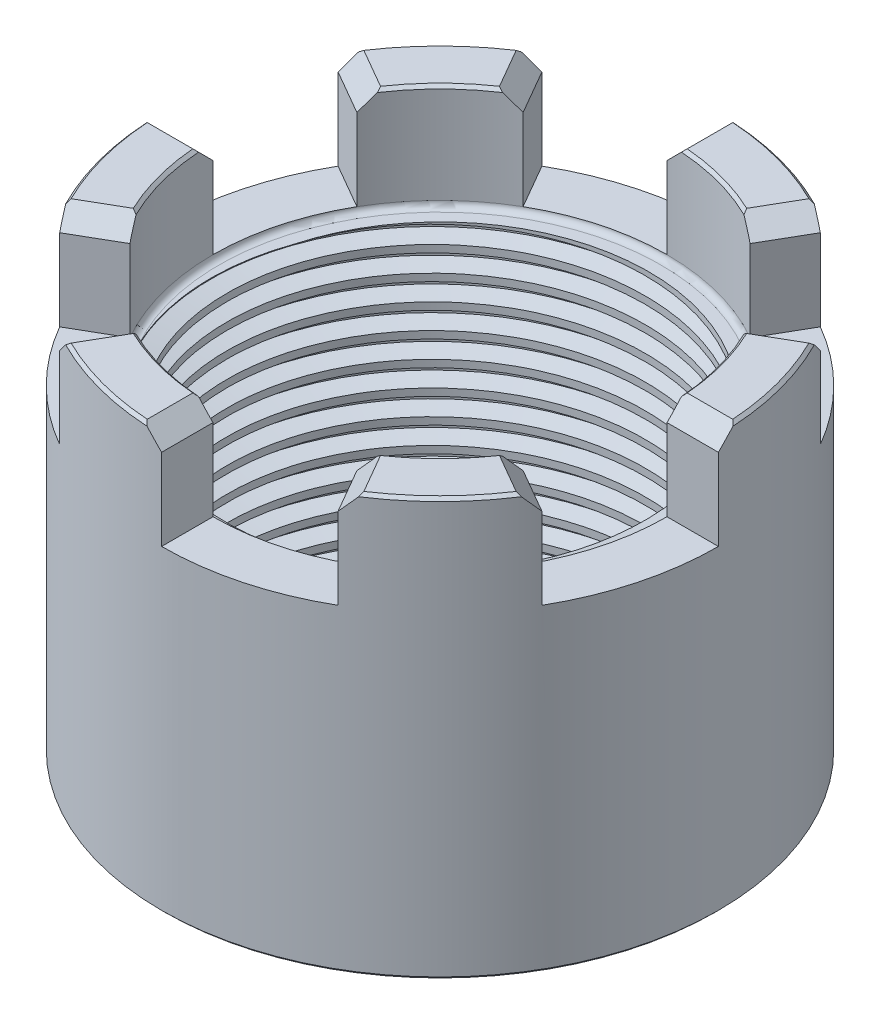
SolidWorks part; units mm, degrees
ref_plane "Front Plane" through (0, 0, 0) normal (0, 0, 1) x (1, 0, 0)
ref_plane "Top Plane" through (0, 0, 0) normal (0, 1, 0) x (1, 0, 0)
ref_plane "Right Plane" through (0, 0, 0) normal (1, 0, 0) x (0, 0, -1)
sketch "Sketch1" plane through (0, 0, 0) normal (0, 1, 0) x (1, 0, 0)
  circle A0 centre (0, 0) radius 35.56
  dimension "D1" = 71.12
extrude "Boss-Extrude1" add sketch "Sketch1" along normal blind 40.64
sketch "Sketch2" plane through (0, 40.64, 0) normal (0, 1, 0) x (1, 0, 0)
  circle A0 centre (0, 0) radius 26.7018
  dimension "D1" = 53.4035
extrude "Cut-Extrude1" cut sketch "Sketch2" against normal blind 67.31
sketch "Sketch3" plane through (0, 40.64, 0) normal (0, 1, 0) x (1, 0, 0)
  line L0 (-28.9941, 0) -> (-35.56, 0)
  line L1 (-25.1096, -14.4971) -> (-30.7959, -17.78)
  line L2 (-25.1096, 14.4971) -> (-30.7959, 17.78)
  line L3 (-14.497, 25.1096) -> (-17.78, 30.7959)
  line L4 (0, 28.9941) -> (0, 35.56)
  line L5 (14.4971, 25.1096) -> (17.78, 30.7959)
  line L6 (25.1096, 14.497) -> (30.7959, 17.78)
  line L7 (28.9941, 0) -> (35.56, 0)
  line L8 (25.1096, -14.4971) -> (30.7959, -17.78)
  line L9 (14.497, -25.1096) -> (17.78, -30.7959)
  line L10 (0, -28.9941) -> (0, -35.56)
  line L11 (-14.4971, -25.1096) -> (-17.78, -30.7959)
  arc A0 (-35.56, 0) -> (-30.7959, -17.78) centre (0, 0) ccw
  arc A1 (-28.9941, 0) -> (-25.1096, -14.4971) centre (0, 0) ccw
  arc A2 (-17.78, 30.7959) -> (-30.7959, 17.78) centre (0, 0) ccw
  arc A3 (-14.497, 25.1096) -> (-25.1096, 14.4971) centre (0, 0) ccw
  arc A4 (17.78, 30.7959) -> (0, 35.56) centre (0, 0) ccw
  arc A5 (14.4971, 25.1096) -> (0, 28.9941) centre (0, 0) ccw
  arc A6 (35.56, 0) -> (30.7959, 17.78) centre (0, 0) ccw
  arc A7 (28.9941, 0) -> (25.1096, 14.497) centre (0, 0) ccw
  arc A8 (17.78, -30.7959) -> (30.7959, -17.78) centre (0, 0) ccw
  arc A9 (14.497, -25.1096) -> (25.1096, -14.4971) centre (0, 0) ccw
  arc A10 (-17.78, -30.7959) -> (0, -35.56) centre (0, 0) ccw
  arc A11 (-14.4971, -25.1096) -> (0, -28.9941) centre (0, 0) ccw
  point P29 (0, 0)
  dimension "D2" = 57.9882
  dimension "D1" = 30
  dimension "D3" = 6
extrude "Boss-Extrude2" add sketch "Sketch3" along normal blind 12.7
chamfer "Chamfer1" distance 2.286 angle 45 1 edges at (0, 53.34, 32.2771)
chamfer "Chamfer2" distance 2.286 angle 45 1 edges at (-16.1385, 53.34, 27.9527)
chamfer "Chamfer3" distance 2.286 angle 45 1 edges at (-27.9527, 53.34, 16.1385)
chamfer "Chamfer4" distance 2.286 angle 45 1 edges at (16.1385, 53.34, 27.9527)
chamfer "Chamfer5" distance 2.286 angle 45 1 edges at (27.9527, 53.34, 16.1385)
chamfer "Chamfer6" distance 2.286 angle 45 1 edges at (32.277, 53.34, 0)
chamfer "Chamfer7" distance 2.286 angle 45 1 edges at (27.9527, 53.34, -16.1385)
chamfer "Chamfer8" distance 2.286 angle 45 1 edges at (16.1385, 53.34, -27.9527)
chamfer "Chamfer9" distance 2.286 angle 45 1 edges at (0, 53.34, -32.2771)
chamfer "Chamfer10" distance 2.286 angle 45 1 edges at (-16.1385, 53.34, -27.9527)
chamfer "Chamfer11" distance 2.286 angle 45 1 edges at (-27.9527, 53.34, -16.1385)
chamfer "Chamfer12" distance 2.286 angle 45 1 edges at (-32.2771, 53.34, 0)
chamfer "Chamfer13" distance 0.381 angle 45 1 edges at (9.2036, 53.34, -34.3483)
chamfer "Chamfer14" distance 0.381 angle 45 1 edges at (-25.1447, 53.34, -25.1447)
chamfer "Chamfer15" distance 0.381 angle 45 1 edges at (-34.3483, 53.34, 9.2036)
chamfer "Chamfer16" distance 0.381 angle 45 1 edges at (-9.2036, 53.34, 34.3483)
chamfer "Chamfer17" distance 0.381 angle 45 1 edges at (25.1447, 53.34, 25.1447)
chamfer "Chamfer18" distance 0.381 angle 45 1 edges at (34.3483, 53.34, -9.2036)
chamfer "Chamfer20" distance 0.381 angle 45 1 edges at (-28.0062, 53.34, 7.5042)
chamfer "Chamfer21" distance 0.381 angle 45 1 edges at (-7.5042, 53.34, 28.0062)
chamfer "Chamfer22" distance 0.381 angle 45 1 edges at (20.5019, 53.34, 20.5019)
chamfer "Chamfer23" distance 0.381 angle 45 1 edges at (-20.5019, 53.34, -20.5019)
chamfer "Chamfer24" distance 0.381 angle 45 1 edges at (7.5042, 53.34, -28.0062)
chamfer "Chamfer25" distance 0.381 angle 45 1 edges at (28.0062, 53.34, -7.5042)
chamfer "Chamfer26" distance 0.381 angle 45 1 edges at (0, 0, 35.56)
sketch "Sketch4" plane through (0, 40.64, 0) normal (0, 1, 0) x (1, 0, 0)
  circle A0 centre (0, 0) radius 28.9941
extrude "Cut-Extrude2" cut sketch "Sketch4" against normal blind 0.762
fillet "Fillet1" radius 0.762 1 edges at (0, 39.878, 28.9941)
chamfer "Chamfer27" distance 2.5591 angle 45 1 edges at (0, 0, 26.7018)
thread "Thread3" pitch 3.175 method cut profile "Thread Profile4" start angle 1, offset 3.302, length 0, pitch 3.175, diameter 53.4035
ref_plane "Plane4" through (-26.6977, 43.18, -0.466) normal (0.0175, 0, -0.9998) x (0.9998, 0, 0.0175)
sketch "Thread Profile4" plane through (-26.6977, 43.18, -0.466) normal (0.0175, 0, -0.9998) x (0.9998, 0, 0.0175)
  line L0 (0, 0) -> (0, 3.175) construction
  line L11 (0, 0) -> (0, 2.2405)
  line L12 (0, 2.2405) -> (-2.0561, 1.7088)
  line L13 (-2.0561, 1.7088) -> (-2.0561, 0.5318)
  line L15 (-2.0561, 0.5318) -> (0, 0)
  line L17 (-2.0561, 1.1203) -> (0, 1.1203) construction
  point P2 (0, 0)
  dimension "D1" = 29
  dimension "Pitch" = 3.175
  dimension "Profile_Land" = 1.177
  dimension "Profile_Height" = 2.0561
